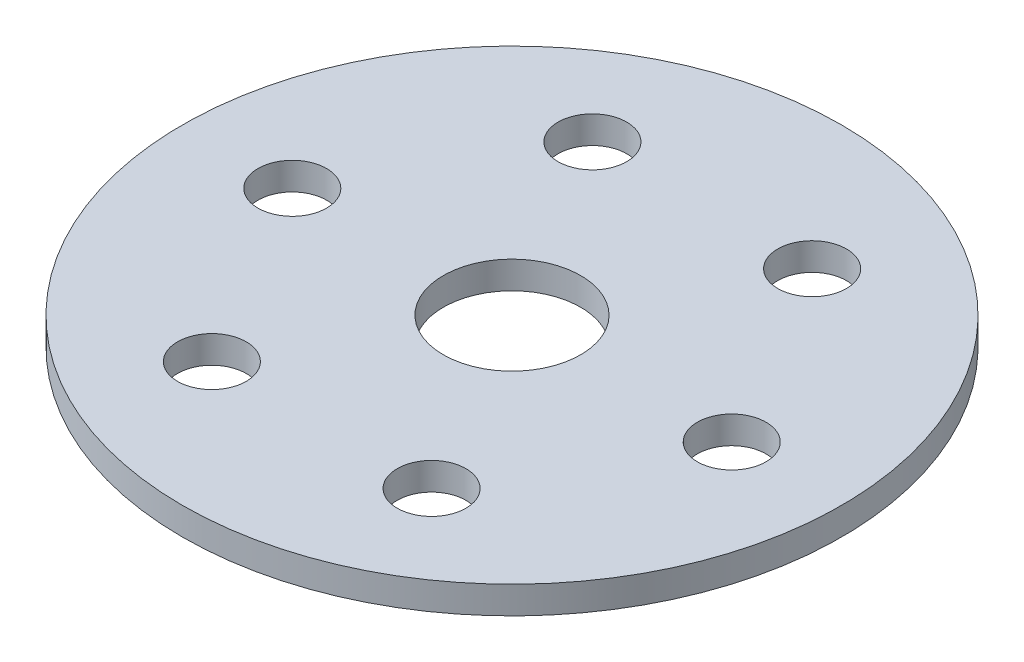
SolidWorks part; units mm, degrees
material "Galvanized Steel"
ref_plane "Front Plane" through (0, 0, 0) normal (0, 0, 1) x (1, 0, 0)
ref_plane "Top Plane" through (0, 0, 0) normal (0, 1, 0) x (1, 0, 0)
ref_plane "Right Plane" through (0, 0, 0) normal (1, 0, 0) x (0, 0, -1)
sketch "Sketch1" plane through (0, 0, 0) normal (0, 1, 0) x (1, 0, 0)
  circle A0 centre (0, 0) radius 76.2
  circle A1 centre (0, 0) radius 15.875
  dimension "D1" = 152.4
  dimension "D2" = 31.75
extrude "Plate extrude" add sketch "Sketch1" along normal blind 6.35
hole_wizard "5/8 (0.625) Diameter Hole1" positions "Sketch2" profile "Sketch3" hole size "5/8" standard "ANSI Inch" end condition through all
sketch "Sketch2" plane through (0, 6.35, 0) normal (0, 1, 0) x (1, 0, 0)
  line L0 (-3.4925, 0) -> (3.4925, 0) construction
  circle A2 centre (0, 0) radius 76.2 construction
  point P0 (-50.8, 0)
  dimension "D1" = 50.8
sketch "Sketch3" plane through (-50.8, 6.35, 0) normal (1, 0, 0) x (0, 0, 1)
  line L0 (0, 0) -> (0, 6.35)
  line L1 (0, 6.35) -> (7.9375, 6.35)
  line L2 (7.9375, 6.35) -> (7.9375, 0)
  line L5 (7.9375, 0) -> (0, 0)
  line L11 (0, -6.35) -> (0, 107.95) construction
  dimension "Thru Hole Dia." = 15.875
  dimension "Thru Hole Depth" = 6.35
pattern_circular "CirPattern1" count 6 over 360 about axis through (0, 6.35, 0) along (0, -1, 0) of "5/8 (0.625) Diameter Hole1" reverse direction yes
